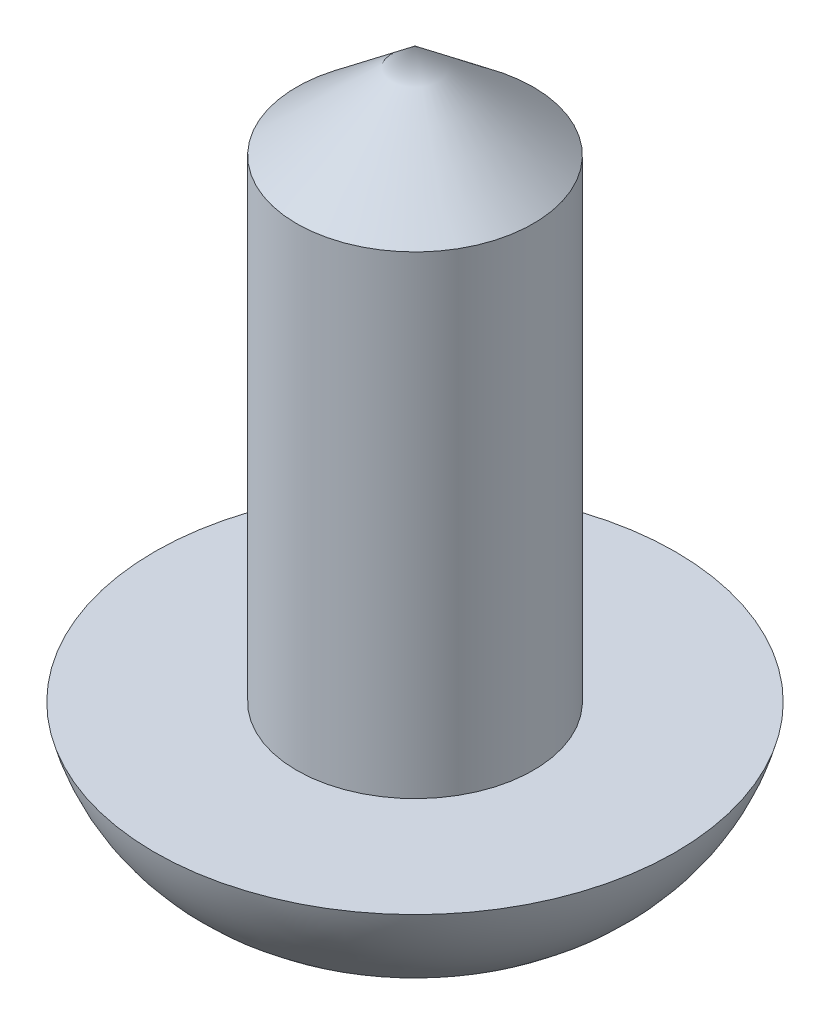
SolidWorks part; units mm, degrees
ref_plane "Front Plane" through (0, 0, 0) normal (0, 0, 1) x (1, 0, 0)
ref_plane "Top Plane" through (0, 0, 0) normal (0, 1, 0) x (1, 0, 0)
ref_plane "Right Plane" through (0, 0, 0) normal (1, 0, 0) x (0, 0, -1)
sketch "Sketch1" plane through (0, 0, 0) normal (0, 1, 0) x (1, 0, 0)
  circle A0 centre (0, 0) radius 1.25
  dimension "D1" = 2.5
extrude "Boss-Extrude1" add sketch "Sketch1" along normal blind 5 contours A0
sketch "Sketch2" plane through (0, 0, 0) normal (0, -1, 0) x (1, 0, 0)
  circle A0 centre (0, 0) radius 2.75
  circle A1 centre (0, 0) radius 1.25 construction
  circle A2 centre (0, 0) radius 1.25 construction
  dimension "D1" = 5.5
extrude "Boss-Extrude2" add sketch "Sketch2" along normal blind 1.5
fillet "Fillet1" radius 2 1 edges at (0, -1.5, -2.75)
sketch "Sketch3" plane through (0, -1.5, 0) normal (0, -1, 0) x (1, 0, 0)
  line L0 (0.375, 0.375) -> (1.5, 0.375)
  line L1 (-0.375, -1.5) -> (0.375, -1.5)
  line L2 (-0.375, -1.5) -> (-0.375, -0.375)
  line L3 (-0.375, 1.5) -> (0.375, 1.5)
  line L4 (0.375, -1.5) -> (0.375, -0.375)
  line L7 (-1.5, -0.375) -> (-0.375, -0.375)
  line L8 (-1.5, -0.375) -> (-1.5, 0.375)
  line L9 (-1.5, 0.375) -> (-0.375, 0.375)
  line L10 (1.5, -0.375) -> (1.5, 0.375)
  line L15 (0.375, 0.375) -> (0.375, 1.5)
  line L16 (0.375, -0.375) -> (1.5, -0.375)
  line L17 (-0.375, 0.375) -> (-0.375, 1.5)
  point P0 (0, 0)
  point P6 (0, 0)
  dimension "D1" = 3
  dimension "D2" = 0.75
extrude "Cut-Extrude1" cut sketch "Sketch3" against normal blind 1 draft 15
sketch "Sketch5" [suppressed] plane through (0, 0, 0) normal (0, 0, 1) x (1, 0, 0)
  line L0 (-2.1, -2) -> (2.1, -2) construction
  line L3 (0, 0) -> (0, 24) construction
  point P6 (0, 11)
  dimension "D1" = 13
  dimension "D2" = 26
sketch "Sketch6" [suppressed] plane through (0, 0, 0) normal (0, 0, 1) x (1, 0, 0)
  line L0 (0, 0) -> (0, 50) construction
  line L1 (4, 50) -> (-4, 50) construction
sketch "Sketch7" [suppressed] plane through (0, 0, 0) normal (1, 0, 0) x (0, 0, -1)
  line L0 (0, 10) -> (0, 50010) construction
  line L1 (1.5875, 25.4) -> (-1.5875, 25.4) construction
  line L2 (-1.5875, 25.4) -> (0, 25.4)
  line L3 (0, 25.4) -> (0, 27.4)
  line L4 (0, 27.4) -> (-1.5875, 25.4)
  point P4 (0, 25.4)
  dimension "D1" = 2
revolve "Revolve1" [suppressed] add sketch "Sketch7" angle 360 about L0
sketch "Sketch8" [suppressed] plane through (0, 0, 0) normal (0, -1, 0) x (1, 0, 0)
  circle A0 centre (0, 0) radius 2.2225
  dimension "D1" = 4.445
extrude "Boss-Extrude3" [suppressed] add sketch "Sketch8" along normal blind 3
sketch "Sketch9" [suppressed] plane through (0, -3, 0) normal (0, -1, 0) x (1, 0, 0)
  circle A0 centre (0, 0) radius 1.2225
  circle A1 centre (0, 0) radius 2.2225 construction
  dimension "D1" = 1
extrude "Cut-Extrude2" [suppressed] cut sketch "Sketch9" against normal offset from surface (2 mm away) 1 up to face at (0, 0, 1.25)
sketch "Sketch11" plane through (0, 0, 0) normal (0, 0, 1) x (1, 0, 0)
  line L0 (0, 5) -> (0, 6)
  line L1 (1.25, 5) -> (-1.25, 5) construction
  line L2 (0, 6) -> (-1.25, 5)
  line L3 (-1.25, 5) -> (0, 5)
  line L4 (-1.25, 5) -> (-1.25, 0) construction
  dimension "D1" = 1
revolve "Revolve2" add sketch "Sketch11" angle 360 about L0
